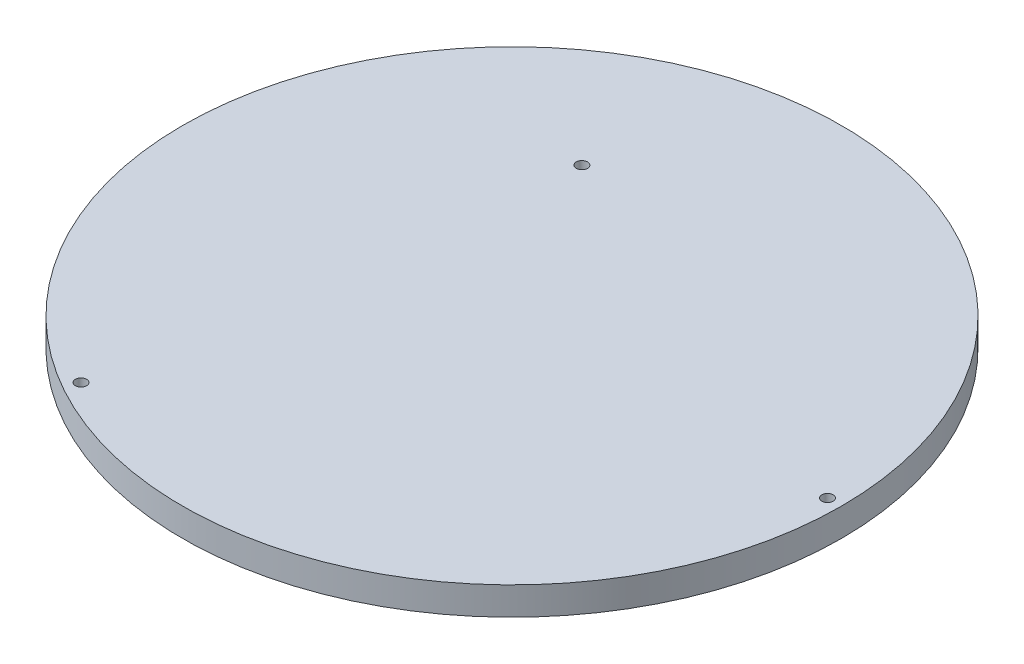
SolidWorks part; units mm, degrees
ref_plane "Front Plane" through (0, 0, 0) normal (0, 0, 1) x (1, 0, 0)
ref_plane "Top Plane" through (0, 0, 0) normal (0, 1, 0) x (1, 0, 0)
ref_plane "Right Plane" through (0, 0, 0) normal (1, 0, 0) x (0, 0, -1)
sketch "Sketch1" plane through (0, 0, 0) normal (0, 0, 1) x (1, 0, 0)
  line L0 (0, -200000) -> (0, 218797.9879) construction
  line L1 (149.225, -24.4122) -> (149.225, -37.1122) construction
  line L2 (0, -24.4122) -> (149.225, -24.4122) construction
  line L3 (149.225, -37.1122) -> (0, -37.1122) construction
  line L4 (0, -200000) -> (0, 218797.9879) construction
  line L5 (149.225, -24.4122) -> (149.225, -37.1122)
  line L6 (0, -24.4122) -> (149.225, -24.4122)
  line L7 (149.225, -37.1122) -> (0, -37.1122)
  line L8 (0, -24.4122) -> (0, -37.1122)
revolve "Revolve1" add sketch "Sketch1" angle 360 about L4
hole_wizard "1/4-20 Tapped Hole1" positions "Sketch2" profile "Sketch3" tap size "1/4-20" standard "ANSI Inch" end condition up to next
sketch "Sketch2" plane through (0, -24.4122, 0) normal (0, 1, 0) x (1, 0, 0)
  line L0 (0, 0) -> (142.875, 0) construction
  line L3 (0, 0) -> (-71.4375, -123.7334) construction
  line L6 (0, 0) -> (-43.2486, 74.9088) construction
  circle A0 centre (0, 0) radius 142.875
  point P0 (142.875, 0)
  point P2 (-71.4375, -123.7334)
  point P4 (-43.2486, 74.9088)
  dimension "D1" = 120
  dimension "D2" = 120
sketch "Sketch3" plane through (142.875, -24.4122, 0) normal (1, 0, 0) x (0, 0, 1)
  line L0 (0, 0) -> (0, 12.7)
  line L1 (0, 12.7) -> (2.5527, 12.7)
  line L2 (2.5527, 12.7) -> (2.5527, 0)
  line L5 (2.5527, 0) -> (0, 0)
  line L11 (0, -6.35) -> (0, 107.95) construction
  dimension "Thru Tap Drill Dia." = 5.1054
  dimension "Thru Tap Drill Depth" = 12.7
cosmetic thread "Hole Thread1" parameters "D2"=6.35
cosmetic thread "Hole Thread2" parameters "D2"=6.35
cosmetic thread "Hole Thread3" parameters "D2"=6.35
